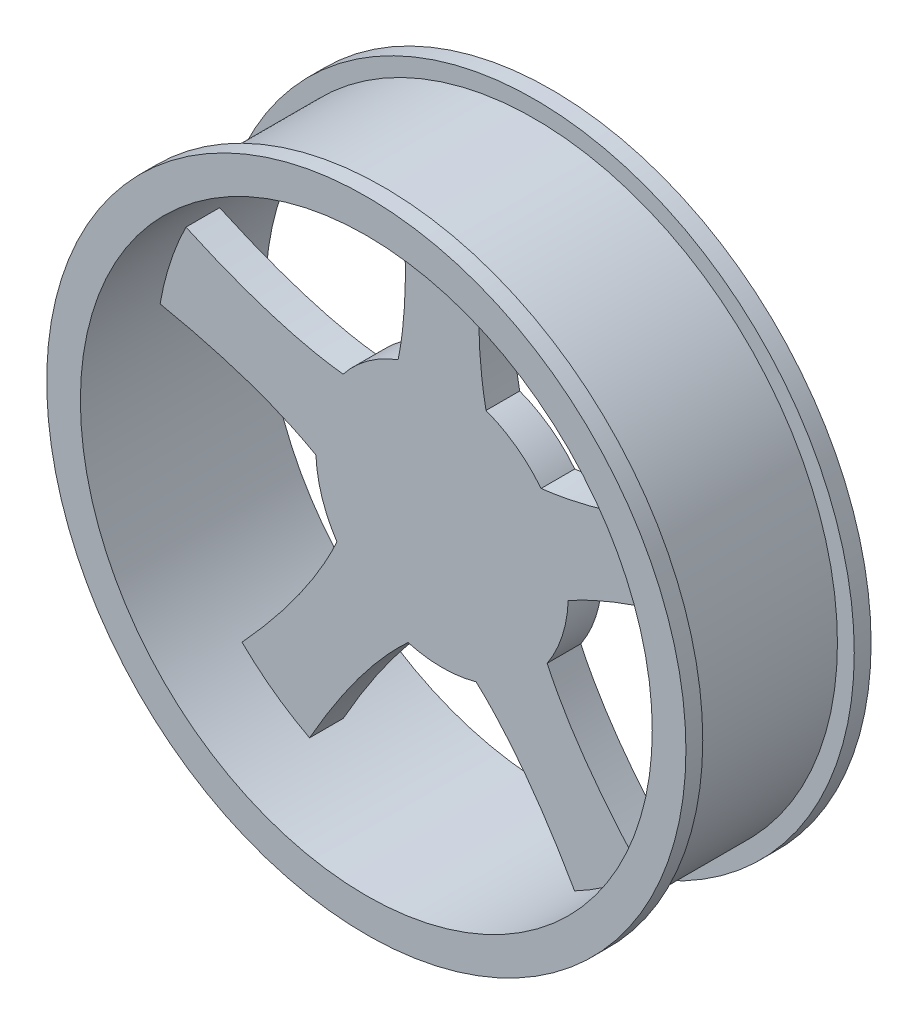
SolidWorks part; units mm, degrees
ref_plane "Front Plane" through (0, 0, 0) normal (0, 0, 1) x (1, 0, 0)
ref_plane "Top Plane" through (0, 0, 0) normal (0, 1, 0) x (1, 0, 0)
ref_plane "Right Plane" through (0, 0, 0) normal (1, 0, 0) x (0, 0, -1)
sketch "Sketch2" plane through (0, 0, 0) normal (1, 0, 0) x (0, 0, -1)
  line L0 (0, 0) -> (0, 35.9709) construction
  line L1 (-9, 35.9709) -> (9, 35.9709)
  line L2 (9, 35.9709) -> (9, 37.9709)
  line L3 (-9, 35.9709) -> (-9, 37.9709)
  line L4 (9, 37.9709) -> (11, 37.9709)
  line L5 (-9, 37.9709) -> (-11, 37.9709)
  line L6 (11, 37.9709) -> (11, 33.9709)
  line L7 (-11, 37.9709) -> (-11, 33.9709)
  line L8 (11, 33.9709) -> (-11, 33.9709)
  line L9 (-10, 0) -> (10, 0)
  point P11 (0, 33.9709)
  point P15 (0, 0)
  dimension "D1" = 18
  dimension "D2" = 2
  dimension "D3" = 2
  dimension "D4" = 4
revolve "Revolve1" add sketch "Sketch2" angle 360 about L9
sketch "Sketch3" plane through (0, 0, 0) normal (0, 0, 1) x (1, 0, 0)
  circle A0 centre (0, 0) radius 15
  circle A1 centre (0, 0) radius 4
  dimension "D1" = 30
  dimension "D2" = 8
extrude "Boss-Extrude1" add sketch "Sketch3" along normal blind 2 and the other way blind 2 separate body contours A0
sketch "Sketch7" plane through (0, 0, 0) normal (0, 0, 1) x (1, 0, 0)
  circle A0 centre (0, 0) radius 4.1
  dimension "D1" = 8.2
sketch "Sketch11" plane through (0, 0, 0) normal (0, 0, 1) x (1, 0, 0)
  line L0 (0, 14.9571) -> (0, 15) construction
  line L1 (0, 33.9709) -> (5, 33.9709)
  line L2 (0, 33.9709) -> (-5, 33.9709)
  line L3 (-5, 33.9709) -> (5, 33.9709)
  line L4 (32.3082, 10.4976) -> (30.7632, 15.2529)
  line L5 (32.3082, 10.4976) -> (33.8533, 5.7423)
  line L6 (19.9676, -27.483) -> (24.0127, -24.5441)
  line L7 (19.9676, -27.483) -> (15.9225, -30.422)
  line L8 (-19.9676, -27.483) -> (-15.9225, -30.422)
  line L9 (-19.9676, -27.483) -> (-24.0127, -24.5441)
  line L10 (-32.3082, 10.4976) -> (-33.8533, 5.7423)
  line L11 (-32.3082, 10.4976) -> (-30.7632, 15.2529)
  circle A0 centre (0, 0) radius 15 construction
  circle A1 centre (0, 0) radius 33.9709 construction
  spline S0 degree 2 poles (5, 33.9709) (3.603, 22.0026) (5.2194, 14.0627) knots 0 0 0 0.277878 0.277878 0.277878
  spline S1 degree 3 poles (5.2194, 14.0627) (2.7127, 14.916) (0.2756, 15.1588) (-2.092, 14.7913) knots 0 0 0 0 0.441009 0.441009 0.441009 0.441009
  spline S2 degree 2 poles (-5, 33.9709) (-3.603, 22.0026) (-5.2194, 14.0627) knots 0 0 0 0.277878 0.277878 0.277878
  spline S3 degree 2 poles (-5.2194, 14.0627) (-2.5171, 14.9241) (0, 14.9571) knots 0 0 0 0.374182 0.374182 0.374182
  spline S4 degree 2 poles (30.7632, 15.2529) (19.8123, 10.2258) (11.7615, 9.3095) knots 0 0 0 0.277878 0.277878 0.277878
  spline S5 degree 2 poles (33.8533, 5.7423) (22.0391, 3.3726) (14.9873, -0.6183) knots 0 0 0 0.277878 0.277878 0.277878
  spline S6 degree 3 poles (14.9873, -0.6183) (15.0242, 2.0294) (14.5021, 4.4223) (13.4209, 6.5604) knots 0 0 0 0 0.441009 0.441009 0.441009 0.441009
  spline S7 degree 2 poles (11.7615, 9.3095) (13.4159, 7.0058) (14.2251, 4.622) knots 0 0 0 0.374182 0.374182 0.374182
  spline S8 degree 2 poles (24.0127, -24.5441) (15.8477, -15.6827) (12.4884, -8.3091) knots 0 0 0 0.277878 0.277878 0.277878
  spline S9 degree 2 poles (15.9225, -30.422) (10.0179, -19.9182) (4.0433, -14.4448) knots 0 0 0 0.277878 0.277878 0.277878
  spline S10 degree 3 poles (4.0433, -14.4448) (6.5728, -13.6618) (8.6872, -12.4257) (10.3866, -10.7367) knots 0 0 0 0 0.441009 0.441009 0.441009 0.441009
  spline S11 degree 2 poles (12.4884, -8.3091) (10.8086, -10.5944) (8.7916, -12.1006) knots 0 0 0 0.374182 0.374182 0.374182
  spline S12 degree 2 poles (-15.9225, -30.422) (-10.0179, -19.9182) (-4.0433, -14.4448) knots 0 0 0 0.277878 0.277878 0.277878
  spline S13 degree 2 poles (-24.0127, -24.5441) (-15.8477, -15.6827) (-12.4884, -8.3091) knots 0 0 0 0.277878 0.277878 0.277878
  spline S14 degree 3 poles (-12.4884, -8.3091) (-10.962, -10.4728) (-9.1331, -12.1018) (-7.0016, -13.196) knots 0 0 0 0 0.441009 0.441009 0.441009 0.441009
  spline S15 degree 2 poles (-4.0433, -14.4448) (-6.7358, -13.5534) (-8.7916, -12.1006) knots 0 0 0 0.374182 0.374182 0.374182
  spline S16 degree 2 poles (-33.8533, 5.7423) (-22.0391, 3.3726) (-14.9873, -0.6183) knots 0 0 0 0.277878 0.277878 0.277878
  spline S17 degree 2 poles (-30.7632, 15.2529) (-19.8123, 10.2258) (-11.7615, 9.3095) knots 0 0 0 0.277878 0.277878 0.277878
  spline S18 degree 3 poles (-11.7615, 9.3095) (-13.3477, 7.1892) (-14.3318, 4.9464) (-14.7138, 2.5811) knots 0 0 0 0 0.441009 0.441009 0.441009 0.441009
  spline S19 degree 2 poles (-14.9873, -0.6183) (-14.9715, 2.2179) (-14.2251, 4.622) knots 0 0 0 0.374182 0.374182 0.374182
  point P49 (0, 0)
  dimension "D1" = 5
  dimension "D2" = 5
  dimension "D3" = 5
extrude "Boss-Extrude3" add sketch "Sketch11" along normal blind 2 and the other way blind 2 contours S16 S19 S18 S17 L11 L10 | S2 S3 S1 S0 L1 L2 | S4 S7 S6 S5 L5 L4 | S8 S11 S10 S9 L7 L6 | S12 S15 S14 S13 L9 L8 region at (-0.0013, 24.3147, 0) region at (23.1242, 7.5149, 0) region at (14.2929, -19.6702, 0) region at (-14.2908, -19.6718, 0) region at (-23.1251, 7.5124, 0)
sketch "Sketch12" plane through (0, 0, 0) normal (0, 0, 1) x (1, 0, 0)
  circle A0 centre (0, 0) radius 10
  dimension "D1" = 20
